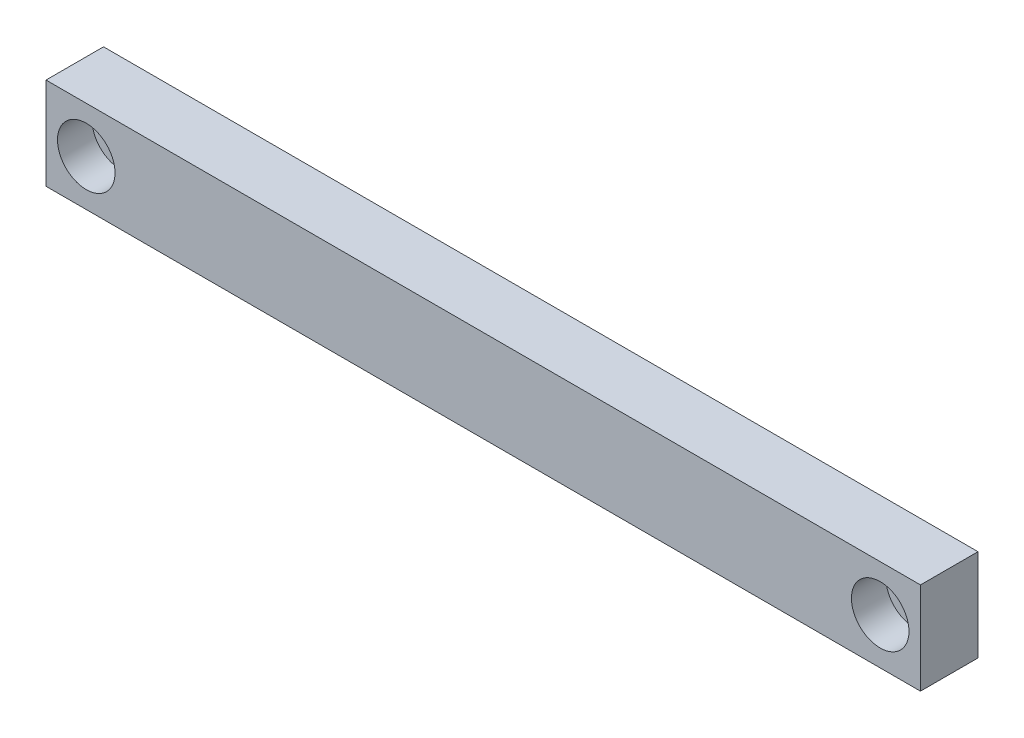
SolidWorks part; units mm, degrees
ref_plane "Front Plane" through (0, 0, 0) normal (0, 0, 1) x (1, 0, 0)
ref_plane "Top Plane" through (0, 0, 0) normal (0, 1, 0) x (1, 0, 0)
ref_plane "Right Plane" through (0, 0, 0) normal (1, 0, 0) x (0, 0, -1)
sketch "Sketch3" plane through (0, 0, 4.5) normal (0, 0, 1) x (1, 0, 0)
  line L0 (-38, 4) -> (38, 4)
  line L1 (38, 4) -> (38, -4)
  line L2 (38, -4) -> (-38, -4)
  line L3 (-38, -4) -> (-38, 4)
  line L4 (0, -55) -> (0, 55) construction
  line L5 (-38, 0) -> (38, 0) construction
  circle A0 centre (-34.5, 0) radius 1.5
  circle A1 centre (34.5, 0) radius 1.5
extrude "Boss-Extrude1" add sketch "Sketch3" along normal blind 5
sketch "Sketch4" plane through (0, 0, 4.5) normal (0, 0, -1) x (-1, 0, 0)
  circle A0 centre (0, 0) radius 3
extrude "Cut-Extrude1" cut sketch "Sketch4" against normal blind 3
sketch "Sketch5" plane through (0, 0, 9.5) normal (0, 0, 1) x (1, 0, 0)
  line L0 (0, -55) -> (0, 55) construction
  circle A0 centre (34.5, 0) radius 2.5
  circle A1 centre (-34.5, 0) radius 2.5
extrude "Cut-Extrude2" cut sketch "Sketch5" against normal blind 3
sketch "Sketch6" plane through (0, 0, 0) normal (0, 1, 0) x (1, 0, 0)
  line L0 (0, 0) -> (0, -40) construction
  line L1 (0, -40) -> (20.8349, -40) construction
  point P3 (0, 0)
ref_axis "Axis2" through (0, 0, 40) along (1, 0, 0)
